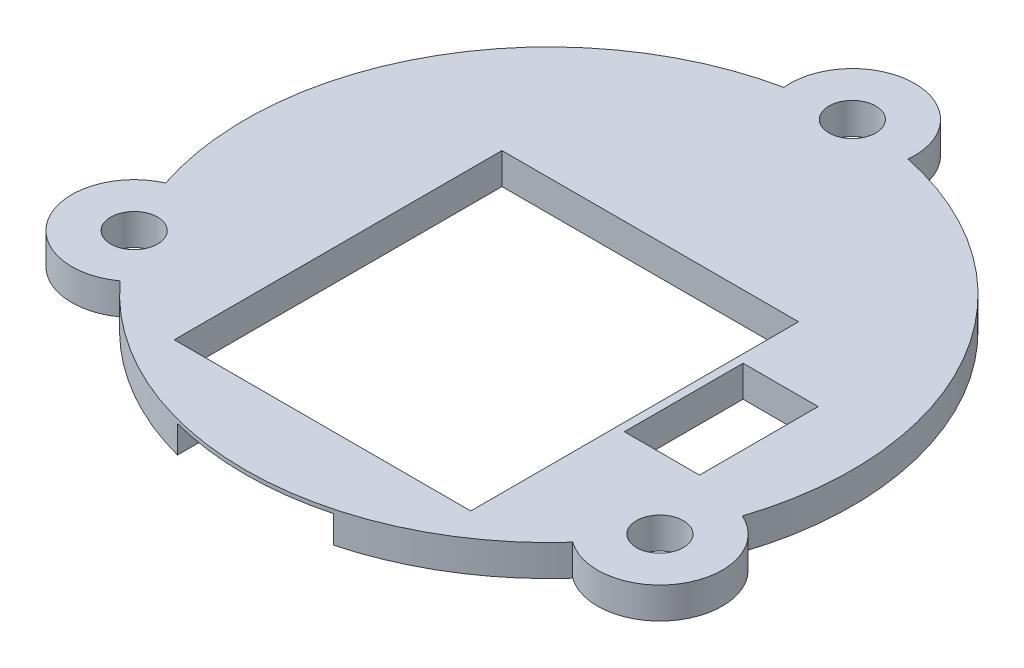
SolidWorks part; units mm, degrees
material "PLA"
ref_plane "Front" through (0, 0, 0) normal (0, 0, 1) x (1, 0, 0)
ref_plane "Top" through (0, 0, 0) normal (0, 1, 0) x (1, 0, 0)
ref_plane "Right" through (0, 0, 0) normal (1, 0, 0) x (0, 0, -1)
other "Configuration Table"
sketch "Esquisse2" plane through (0, 0, 0) normal (0, 1, 0) x (1, 0, 0)
  line L0 (0, 19.45) -> (0, 0) construction
  circle A0 centre (0, 0) radius 19.45
  circle A1 centre (0, 19.45) radius 1.5
  circle A2 centre (0, 19.45) radius 4
  dimension "D1" = 38.9
  dimension "D2" = 3
  dimension "D3" = 8
extrude "Boss.-Extru.1" add sketch "Esquisse2" along normal blind 2 contours A2 A0 | L0 A0 A1 | L0 A1 A0 A2 | A1 L0 A2 A0 | A0 L0 A1 region at (0.6285, 0, -18.8031) region at (-0.6285, 0, -18.8031) region at (1.8091, 0, -17.4906) region at (-1.8091, 0, -17.4906) region at (0, 0, 0.3649)
extrude "Boss.-Extru.2" add sketch "Esquisse2<3>" along normal up to surface (2 mm away) contours A0 A2 A1 region at (0, 0, -21.2294) up to face at (0, 2, 19.45)
sketch "Esquisse2<3>" plane through (0, 0, 0) normal (0, 1, 0) x (1, 0, 0) same geometry as "Esquisse2"
extrude "Enlèv. mat.-Extru.2" cut sketch "Esquisse2<4>" along normal up to surface (2 mm away) contours A0 L0 A1 | L0 A0 A1 region at (0.6285, 0, -18.8031) region at (-0.6285, 0, -18.8031) up to face at (0, 2, -2)
sketch "Esquisse2<4>" plane through (0, 0, 0) normal (0, 1, 0) x (1, 0, 0) same geometry as "Esquisse2"
pattern_circular "Répétition circulaire1" count 2 every 120 about axis through (0, 2, 0) along (0, -1, 0) of "Enlèv. mat.-Extru.2", "Boss.-Extru.2" other way count 2
sketch "Esquisse5" plane through (0, 0, 0) normal (0, -1, 0) x (1, 0, 0)
  line L0 (10.8435, -16.1468) -> (-16.1468, 10.8435)
  line L1 (10.8435, -16.1468) -> (16.1468, -10.8435)
  line L2 (-16.1468, 10.8435) -> (-10.8435, 16.1468)
  line L3 (16.1468, -10.8435) -> (-10.8435, 16.1468)
  line L4 (10.8435, -16.1468) -> (-10.8435, 16.1468) construction
  line L5 (-16.1468, 10.8435) -> (16.1468, -10.8435) construction
  line L6 (0, 0) -> (0, 19.45) construction
  line L7 (-16.1468, -10.8435) -> (10.8435, 16.1468)
  line L8 (-16.1468, -10.8435) -> (-10.8435, -16.1468)
  line L9 (10.8435, 16.1468) -> (16.1468, 10.8435)
  line L10 (-10.8435, -16.1468) -> (16.1468, 10.8435)
  line L11 (-16.1468, -10.8435) -> (16.1468, 10.8435) construction
  line L12 (10.8435, 16.1468) -> (-10.8435, -16.1468) construction
  line L13 (0, 0) -> (13.4952, 13.4952)
  line L14 (0, 0) -> (-13.4952, 13.4952)
  arc A0 (14.4986, 12.9651) -> (-14.4986, 12.9651) centre (0, 0) ccw construction
  circle A1 centre (0, 0) radius 17.45
  circle A2 centre (0, 0) radius 16.45
  point P1 (0, 0)
  dimension "D5" = 34.9
  dimension "D1" = 7.5
  dimension "D2" = 45
  dimension "D3" = 7.5
  dimension "D4" = 45
  dimension "D6" = 1
extrude "Boss.-Extru.3" add sketch "Esquisse5" along normal blind 0.8 contours A2 L0 A1 L3 | A2 L7 A1 L10 | A2 L10 A1 L13 | A2 L14 A1 L0 region at (11.8862, 0, -11.8862) region at (-11.8862, 0, -11.8862) region at (-13.2176, 0, 10.5548) region at (13.2176, 0, 10.5548)
fillet "Congé1" radius 2 10 edges at (14.3398, 0, -9.0365) (9.0365, 0, -14.3398) (-9.0365, 0, -14.3398) (-14.3398, 0, -9.0365) (-14.3398, 0, 9.0365) (14.3398, 0, 9.0365) (-11.6319, 0, -11.6319) (11.6319, 0, -11.6319) (-12.8897, 0, 10.2204) (12.8897, 0, 10.2204)
sketch "Esquisse6" plane through (0, 0, 0) normal (0, -1, 0) x (1, 0, 0)
  line L1 (14.8368, 5.1809) -> (10.0241, 5.1809)
  line L2 (14.8368, 5.1809) -> (14.8368, -2.4223)
  line L3 (14.8368, -2.4223) -> (10.0241, -2.4223)
  line L4 (10.0241, 5.1809) -> (10.0241, -2.4223)
  point P4 (9.0485, 5.8007)
  point P5 (13.8613, -1.8024)
extrude "Enlèv. mat.-Extru.3" cut sketch "Esquisse6" against normal blind 10
sketch "Esquisse7" plane through (0, 0, 0) normal (0, -1, 0) x (1, 0, 0)
  line L1 (-9.5, 14.5) -> (9.5, 14.5)
  line L2 (-9.5, 14.5) -> (-9.5, -6.5)
  line L3 (-9.5, -6.5) -> (9.5, -6.5)
  line L4 (9.5, 14.5) -> (9.5, -6.5)
  line L5 (-9.5, 14.5) -> (9.5, -6.5) construction
  line L6 (-9.5, -6.5) -> (9.5, 14.5) construction
  point P10 (0, 4)
  arc M20 (13.5784, 6.0124) -> (10.5005, 10.5005) centre (0, 0) ccw
  arc M24 (-10.5005, 10.5005) -> (-13.5784, 6.0124) centre (0, 0) ccw
  dimension "D1" = 4
  dimension "D2" = 21
  dimension "D3" = 19
extrude "Enlèv. mat.-Extru.4" cut sketch "Esquisse7" against normal blind 3.5 contours L4 L1 L2 L3 M20 M24 region at (0, 0, 4)
sketch "Esquisse8" plane through (0, 0, 0) normal (0, -1, 0) x (1, 0, 0)
  line L1 (-5, 13.4403) -> (5, 13.4403)
  line L2 (-5, 13.4403) -> (-5, 19.6873)
  line L3 (-5, 19.6873) -> (5, 19.6873)
  line L4 (5, 13.4403) -> (5, 19.6873)
  line L5 (-5, 13.4403) -> (5, 19.6873) construction
  line L6 (-5, 19.6873) -> (5, 13.4403) construction
  point P0 (0, 16.5638)
  dimension "D1" = 10
extrude "Enlèv. mat.-Extru.5" cut sketch "Esquisse8" against normal blind 1.75
sketch "Esquisse9" plane through (0, 2, 0) normal (0, 1, 0) x (1, 0, 0)
  line L1 (19.6442, -8.1084) -> (16.8442, -6.4918)
  line L2 (16.8442, -6.4918) -> (14.0442, -8.1084)
  line L3 (14.0442, -8.1084) -> (14.0442, -11.3416)
  line L4 (14.0442, -11.3416) -> (16.8442, -12.9582)
  line L5 (16.8442, -12.9582) -> (19.6442, -11.3416)
  line L6 (19.6442, -11.3416) -> (19.6442, -8.1084)
  line L7 (2.8, 21.0666) -> (0, 22.6832)
  line L8 (0, 22.6832) -> (-2.8, 21.0666)
  line L9 (-2.8, 21.0666) -> (-2.8, 17.8334)
  line L10 (-2.8, 17.8334) -> (0, 16.2168)
  line L11 (0, 16.2168) -> (2.8, 17.8334)
  line L12 (2.8, 17.8334) -> (2.8, 21.0666)
  line L13 (-14.0442, -8.1084) -> (-16.8442, -6.4918)
  line L14 (-16.8442, -6.4918) -> (-19.6442, -8.1084)
  line L15 (-19.6442, -8.1084) -> (-19.6442, -11.3416)
  line L16 (-19.6442, -11.3416) -> (-16.8442, -12.9582)
  line L17 (-16.8442, -12.9582) -> (-14.0442, -11.3416)
  line L18 (-14.0442, -11.3416) -> (-14.0442, -8.1084)
  circle A0 centre (16.8442, -9.725) radius 2.8 construction
  circle A1 centre (0, 19.45) radius 2.8 construction
  circle A2 centre (-16.8442, -9.725) radius 2.8 construction
  circle A3 centre (16.8442, -9.725) radius 1.5 construction
  circle A4 centre (-16.8442, -9.725) radius 1.5 construction
  circle A5 centre (0, 19.45) radius 1.5 construction
  dimension "D1" = 5.6
extrude "Enlèv. mat.-Extru.6" [suppressed] cut sketch "Esquisse9" against normal blind 2.5
